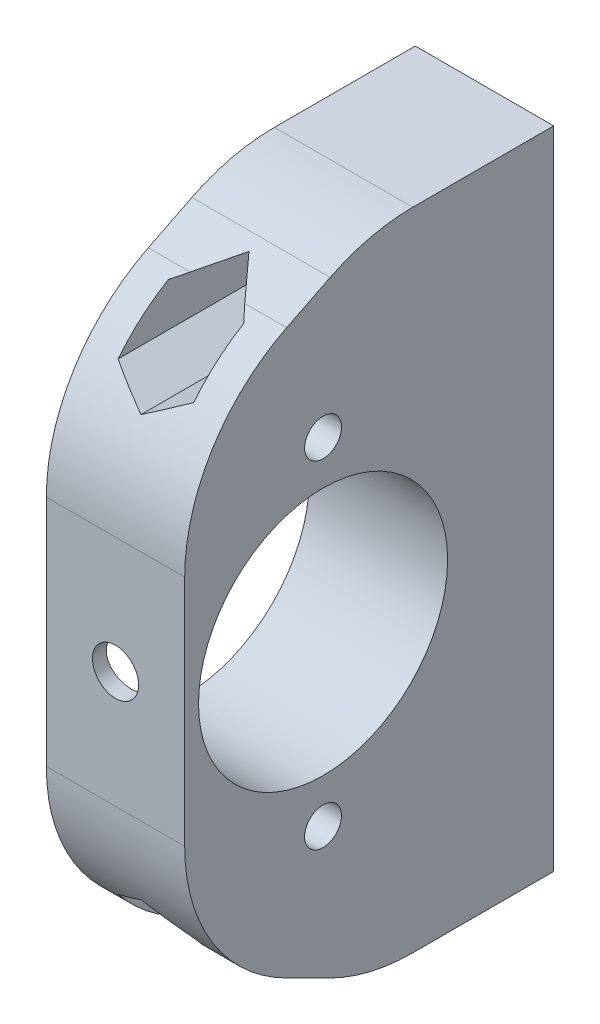
SolidWorks part; units mm, degrees
ref_plane "Front Plane" through (0, 0, 0) normal (0, 0, 1) x (1, 0, 0)
ref_plane "Top Plane" through (0, 0, 0) normal (0, 1, 0) x (1, 0, 0)
ref_plane "Right Plane" through (0, 0, 0) normal (1, 0, 0) x (0, 0, -1)
sketch "Sketch1" plane through (0, 0, 0) normal (1, 0, 0) x (0, 0, -1)
  line L0 (10, 0) -> (10, 18.25) construction
  line L1 (25, 35) -> (9.7214, 35)
  line L5 (25, -35) -> (25, 35) construction
  line L6 (25, -35) -> (25, 35)
  line L7 (10, 18.25) -> (0, 18.25) construction
  line L8 (10, 0) -> (0, 0) construction
  line L9 (0.7771, 32.8885) -> (-3.9443, 30.5279)
  line L10 (0.7771, -32.8885) -> (-3.9443, -30.5279)
  line L14 (-15, 12.6393) -> (-15, -12.6393)
  line L19 (25, -35) -> (9.7214, -35)
  circle A0 centre (0, 18.25) radius 2
  circle A2 centre (0, 0) radius 13.5
  circle A3 centre (0, -18.25) radius 2
  arc A4 (9.7214, 35) -> (0.7771, 32.8885) centre (9.7214, 15) ccw
  arc A5 (9.7214, -35) -> (0.7771, -32.8885) centre (9.7214, -15) cw
  arc A6 (-3.9443, -30.5279) -> (-15, -12.6393) centre (5, -12.6393) cw
  arc A7 (-3.9443, 30.5279) -> (-15, 12.6393) centre (5, 12.6393) ccw
  point P0 (0, 0)
  point P1 (-15, -35)
  point P4 (-15, 35)
  point P30 (5, 35)
  point P33 (5, -35)
  point P36 (-15, -25)
  point P39 (-15, 25)
  dimension "D3" = 27
  dimension "D4" = 4
  dimension "D11" = 20
  dimension "D12" = 20
  dimension "D13" = 20
  dimension "D14" = 20
  dimension "D1" = 18.25
  dimension "D2" = 10
  dimension "D5" = 70
  dimension "D6" = 40
  dimension "D7" = 10
  dimension "D8" = 20
  dimension "D9" = 20
  dimension "D10" = 10
extrude "Boss-Extrude1" add sketch "Sketch1" along normal mid plane 15
sketch "Sketch2" plane through (0, 0, 15) normal (0, 0, 1) x (1, 0, 0)
  line L0 (7.5, -35) -> (-7.5, -35) construction
  line L2 (7.5, 35) -> (-7.5, 35) construction
  line L4 (-7.5, -35) -> (-7.5, 35) construction
  line L5 (7.5, 35) -> (7.5, -35) construction
  line L6 (0, -35) -> (0, 35) construction
  line L7 (-7.5, -27.5) -> (7.5, -27.5) construction
  line L8 (-7.5, 27.5) -> (7.5, 27.5) construction
  line L9 (7.5, -35) -> (-7.5, -35) construction
  line L10 (0, -22.7657) -> (-4.1, -25.1329)
  line L11 (-4.1, -25.1329) -> (-4.1, -29.8671)
  line L12 (-4.1, -29.8671) -> (0, -32.2343)
  line L13 (0, -32.2343) -> (4.1, -29.8671)
  line L14 (4.1, -29.8671) -> (4.1, -25.1329)
  line L15 (4.1, -25.1329) -> (0, -22.7657)
  line L16 (0, 32.2343) -> (-4.1, 29.8671)
  line L17 (-4.1, 29.8671) -> (-4.1, 25.1329)
  line L18 (-4.1, 25.1329) -> (0, 22.7657)
  line L19 (0, 22.7657) -> (4.1, 25.1329)
  line L20 (4.1, 25.1329) -> (4.1, 29.8671)
  line L21 (4.1, 29.8671) -> (0, 32.2343)
  line L22 (7.5, 35) -> (-7.5, 35) construction
  line L23 (7.5, -35) -> (-7.5, -35) construction
  circle A0 centre (0, -27.5) radius 4.1 construction
  circle A1 centre (0, 27.5) radius 4.1 construction
  circle A2 centre (0, 27.5) radius 2.6
  circle A3 centre (0, -27.5) radius 2.6
  dimension "D2" = 8.2
  dimension "D3" = 8.2
  dimension "D5" = 5.2
  dimension "D1" = 7.5
  dimension "D4" = 7.5
extrude "Cut-Extrude1" cut sketch "Sketch2" against normal blind 20
sketch "Sketch4" plane through (0, 0, 15) normal (0, 0, 1) x (1, 0, 0)
  circle A0 centre (0, 0) radius 2.5
  dimension "D1" = 5
extrude "Cut-Extrude2" cut sketch "Sketch4" against normal blind 10
extrude "Cut-Extrude3" cut sketch "Sketch2<3>" against normal through all contours A2 | A3 region at (0, 27.5, 15) region at (0, -27.5, 15)
sketch "Sketch2<3>" plane through (0, 0, 15) normal (0, 0, 1) x (1, 0, 0) same geometry as "Sketch2"
